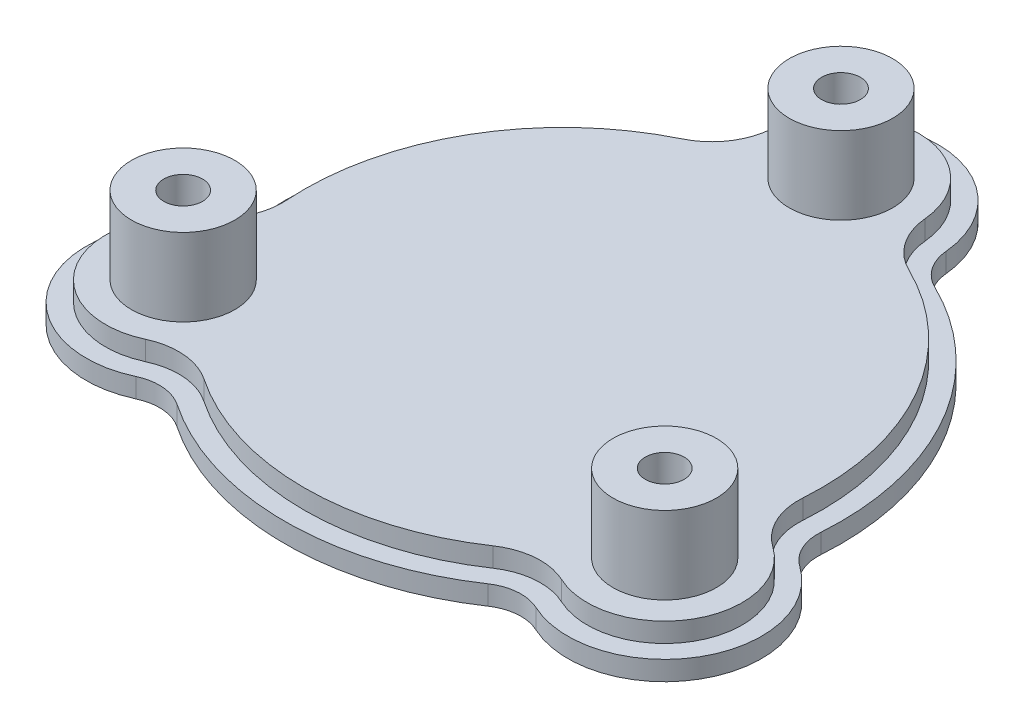
SolidWorks part; units mm, degrees
ref_plane "Front Plane" through (0, 0, 0) normal (0, 0, 1) x (1, 0, 0)
ref_plane "Top Plane" through (0, 0, 0) normal (0, 1, 0) x (1, 0, 0)
ref_plane "Right Plane" through (0, 0, 0) normal (1, 0, 0) x (0, 0, -1)
sketch "Sketch1" plane through (0, 0, 0) normal (0, 1, 0) x (1, 0, 0)
  arc A0 (-18.8462, 38.65) -> (-42.895, -3.0038) centre (0, 0) ccw
  circle A1 centre (0, 43) radius 3
  circle A2 centre (0, 43) radius 6
  arc A3 (14.9415, 44.324) -> (-14.9415, 44.324) centre (0, 43) ccw
  arc A4 (30.915, -35.1017) -> (45.8564, -9.2223) centre (37.2391, -21.5) ccw
  circle A5 centre (37.2391, -21.5) radius 6
  circle A6 centre (37.2391, -21.5) radius 3
  arc A7 (-45.8564, -9.2223) -> (-30.915, -35.1017) centre (-37.2391, -21.5) ccw
  circle A8 centre (-37.2391, -21.5) radius 6
  circle A9 centre (-37.2391, -21.5) radius 3
  arc A10 (-24.0488, -35.6462) -> (24.0488, -35.6462) centre (0, 0) ccw
  arc A11 (42.895, -3.0038) -> (18.8462, 38.65) centre (0, 0) ccw
  arc A12 (38.6475, -18.8512) -> (39.8693, -16.1072) centre (0, 0) ccw
  arc A13 (42.895, -3.0038) -> (45.8564, -9.2223) centre (49.8779, -3.4927) ccw
  arc A14 (24.0488, -35.6462) -> (30.915, -35.1017) centre (27.9637, -41.4491) cw
  arc A15 (-24.0488, -35.6462) -> (-30.915, -35.1017) centre (-27.9637, -41.4491) ccw
  arc A16 (-42.895, -3.0038) -> (-45.8564, -9.2223) centre (-49.8779, -3.4927) cw
  arc A17 (-18.8462, 38.65) -> (-14.9415, 44.324) centre (-21.9141, 44.9419) ccw
  arc A18 (18.8462, 38.65) -> (14.9415, 44.324) centre (21.9141, 44.9419) cw
  circle A31 centre (0, 43) radius 8
  circle A32 centre (-37.2391, -21.5) radius 8
  circle A33 centre (37.2391, -21.5) radius 8
  arc A34 (-17.5313, 35.9535) -> (-39.9023, -2.7942) centre (0, 0) ccw
  arc A35 (-39.9023, -2.7942) -> (-44.133, -11.6779) centre (-49.8779, -3.4927) cw
  arc A36 (-44.133, -11.6779) -> (-32.1798, -32.3813) centre (-37.2391, -21.5) ccw
  arc A37 (-22.371, -33.1593) -> (-32.1798, -32.3813) centre (-27.9637, -41.4491) ccw
  arc A38 (-22.371, -33.1593) -> (22.371, -33.1593) centre (0, 0) ccw
  arc A39 (22.371, -33.1593) -> (32.1798, -32.3813) centre (27.9637, -41.4491) cw
  arc A40 (32.1798, -32.3813) -> (44.133, -11.6779) centre (37.2391, -21.5) ccw
  arc A41 (39.9023, -2.7942) -> (44.133, -11.6779) centre (49.8779, -3.4927) ccw
  arc A42 (39.9023, -2.7942) -> (17.5313, 35.9535) centre (0, 0) ccw
  arc A43 (17.5313, 35.9535) -> (11.9532, 44.0592) centre (21.9141, 44.9419) cw
  arc A44 (11.9532, 44.0592) -> (-11.9532, 44.0592) centre (0, 43) ccw
  arc A45 (-17.5313, 35.9535) -> (-11.9532, 44.0592) centre (-21.9141, 44.9419) ccw
  point P18 (0, 0)
  dimension "D1" = 86
  dimension "D2" = 6
  dimension "D3" = 12
  dimension "D4" = 30
  dimension "D6" = 7
  dimension "D7" = 7
  dimension "D9" = 16
  dimension "D10" = 16
  dimension "D11" = 16
  dimension "D8" = 3
  dimension "D5" = 3
extrude "Boss-Extrude3" add sketch "Sketch1" along normal blind 3 contours A11 A18 A3 A17 A0 A16 A7 A15 A10 A14 A4 A13 A34 A45 A44 A43 A42 A41 A40 A39 A38 A37 A36 A35 region at (-14.9506, 0, -40.1497)
extrude "Boss-Extrude4" add sketch "Sketch1<5>" along normal blind 6 contours A45 A34 A35 A36 A37 A38 A39 A40 A41 A42 A43 A44 A33 A32 A31 region at (0, 0, 0)
sketch "Sketch1<5>" plane through (0, 0, 0) normal (0, 1, 0) x (1, 0, 0) same geometry as "Sketch1"
extrude "Boss-Extrude5" add sketch "Sketch1<6>" along normal blind 18 contours A32 | A33 | A31
sketch "Sketch1<6>" plane through (0, 0, 0) normal (0, 1, 0) x (1, 0, 0) same geometry as "Sketch1"
extrude "Cut-Extrude1" cut sketch "Sketch1<7>" along normal blind 12 contours A8 | A5 | A2
sketch "Sketch1<7>" plane through (0, 0, 0) normal (0, 1, 0) x (1, 0, 0) same geometry as "Sketch1"
extrude "Cut-Extrude2" cut sketch "Sketch1<8>" along normal blind 125 contours A1 | A9 | A6 region at (0, 0, -43)
sketch "Sketch1<8>" plane through (0, 0, 0) normal (0, 1, 0) x (1, 0, 0) same geometry as "Sketch1"
